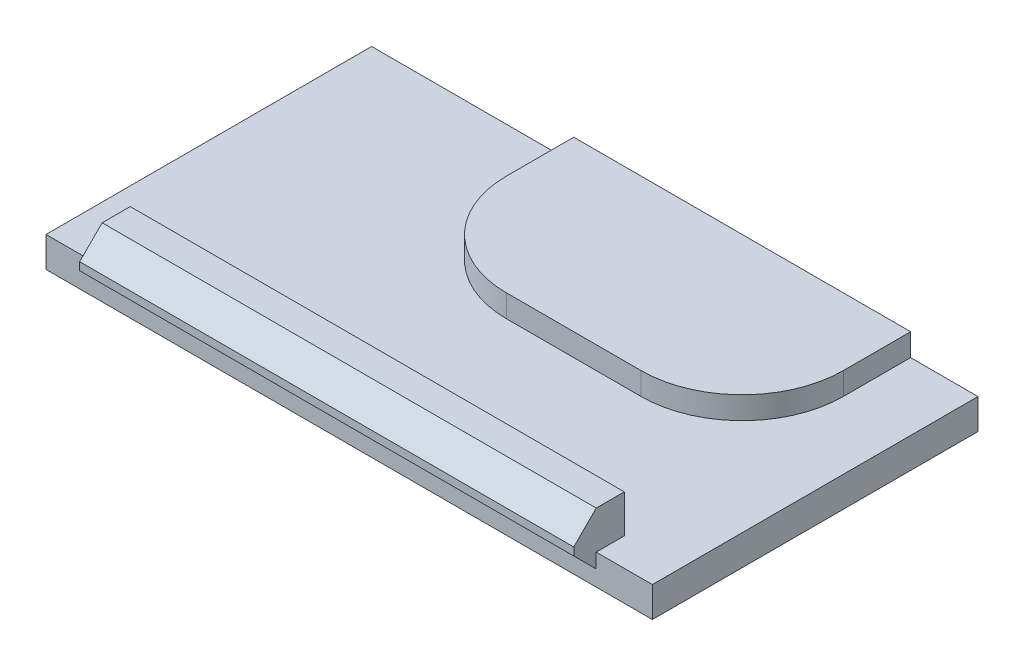
SolidWorks part; units mm, degrees
ref_plane "Front Plane" through (0, 0, 0) normal (0, 0, 1) x (1, 0, 0)
ref_plane "Top Plane" through (0, 0, 0) normal (0, 1, 0) x (1, 0, 0)
ref_plane "Right Plane" through (0, 0, 0) normal (1, 0, 0) x (0, 0, -1)
sketch "Sketch1" plane through (0, 0, 0) normal (0, 1, 0) x (1, 0, 0)
  line L1 (0, 0) -> (68.58, 0)
  line L2 (0, 0) -> (0, 36.83)
  line L3 (0, 36.83) -> (68.58, 36.83)
  line L4 (68.58, 0) -> (68.58, 36.83)
  dimension "D1" = 68.58
  dimension "D2" = 36.83
extrude "Boss-Extrude1" add sketch "Sketch1" along normal blind 3.429
sketch "Sketch3" plane through (0, 0, 0) normal (0, -1, 0) x (1, 0, 0)
  line L0 (34.29, 0) -> (34.29, -21.59) construction
  line L1 (0, 0) -> (68.58, 0) construction
  line L2 (68.58, -36.83) -> (0, -36.83) construction
  line L10 (34.29, -21.59) -> (49.53, -21.59)
  line L11 (57.15, -29.21) -> (57.15, -36.83)
  line L14 (26.67, -29.21) -> (26.67, -36.83)
  line L16 (57.15, -36.83) -> (26.67, -36.83)
  arc A2 (34.29, -21.59) -> (26.67, -29.21) centre (34.29, -29.21) ccw
  arc A3 (57.15, -29.21) -> (49.53, -21.59) centre (49.53, -29.21) ccw
  dimension "D1" = 15.24
  dimension "D3" = 7.62
  dimension "D2" = 15.24
  dimension "D4" = 7.62
  dimension "D5" = 15.24
extrude "Cut-Extrude1" cut sketch "Sketch3" against normal up to surface (3.429 mm away) up to face at (34.29, 3.429, -18.415)
sketch "Sketch5" plane through (0, 0, 0) normal (0, 0, 1) x (1, 0, 0)
  line L0 (0, 3.429) -> (0, 0) construction
  line L1 (6.35, 1.5875) -> (62.23, 1.5875)
  line L2 (6.35, 1.5875) -> (6.35, 7.9375)
  line L3 (6.35, 7.9375) -> (62.23, 7.9375)
  line L4 (62.23, 1.5875) -> (62.23, 7.9375)
  line L5 (68.58, 3.429) -> (68.58, 0) construction
  line L6 (0, 0) -> (68.58, 0) construction
  dimension "D1" = 6.35
  dimension "D2" = 6.35
  dimension "D3" = 1.5875
  dimension "D4" = 6.35
extrude "Boss-Extrude3" add sketch "Sketch5" along normal blind 2.54
chamfer "Chamfer1" distance 2.7305 angle 45 2 edges at (34.29, 1.5875, 2.54) (34.29, 7.9375, 2.54)
sketch "Sketch6" plane through (0, 0, 0) normal (0, 0, -1) x (-1, 0, 0)
  line L5 (-62.23, 7.747) -> (-6.35, 7.747)
  line L6 (-62.23, 7.747) -> (-62.23, 3.429)
  line L7 (-62.23, 3.429) -> (-6.35, 3.429)
  line L8 (-6.35, 7.747) -> (-6.35, 3.429)
extrude "Boss-Extrude4" add sketch "Sketch6" along normal blind 3.175
sketch "Sketch7" plane through (0, 0, 0) normal (0, -1, 0) x (1, 0, 0)
  line L0 (0, -8.255) -> (68.58, -8.255) construction
  line L1 (0, -36.83) -> (0, 0) construction
  line L2 (68.58, 0) -> (68.58, -36.83) construction
  line L4 (49.53, -21.59) -> (34.29, -21.59) construction
  text T0 "<b>BATTERY</b>" font "Arial Rounded MT Bold" height 6.35
  dimension "D1" = 13.335
extrude "Cut-Extrude2" cut sketch "Sketch7" against normal blind 1.016
sketch "Sketch8" plane through (0, 3.429, 0) normal (0, 1, 0) x (1, 0, 0)
  line L0 (60.96, 36.83) -> (60.96, 17.78)
  line L1 (68.58, 36.83) -> (57.15, 36.83) construction
  line L2 (34.29, 17.78) -> (60.96, 17.78)
  line L3 (22.86, 29.21) -> (22.86, 36.83)
  line L4 (26.67, 36.83) -> (0, 36.83) construction
  line L5 (26.67, 29.21) -> (26.67, 36.83) construction
  line L6 (57.15, 36.83) -> (57.15, 29.21) construction
  line L11 (49.53, 21.59) -> (34.29, 21.59) construction
  line L12 (60.96, 36.83) -> (22.86, 36.83)
  arc A0 (22.86, 29.21) -> (34.29, 17.78) centre (34.29, 29.21) ccw
  arc A1 (26.67, 29.21) -> (34.29, 21.59) centre (34.29, 29.21) ccw construction
  arc A2 (49.53, 17.78) -> (60.96, 29.21) centre (49.53, 29.21) ccw
  arc A3 (49.53, 21.59) -> (57.15, 29.21) centre (49.53, 29.21) ccw construction
  line M8 (68.58, 36.83) -> (57.15, 36.83)
  line M9 (57.15, 36.83) -> (57.15, 29.21)
  arc M10 (57.15, 29.21) -> (49.53, 21.59) centre (49.53, 29.21) cw
  line M11 (49.53, 21.59) -> (34.29, 21.59)
  arc M12 (34.29, 21.59) -> (26.67, 29.21) centre (34.29, 29.21) cw
  line M13 (26.67, 29.21) -> (26.67, 36.83)
  line M14 (26.67, 36.83) -> (0, 36.83)
  dimension "D1" = 3.81
  dimension "D2" = 3.81
  dimension "D3" = 3.81
extrude "Boss-Extrude5" add sketch "Sketch8" along normal blind 2.54 contours L2 A2 L0 L3 A0 M8 M9 M10 M11 M12 M13 M14 | L12 M9 M13 M12 M11 M10 region at (60.534, 3.429, -33.02) region at (41.91, 3.429, -29.5455)
sketch "Sketch9" plane through (0, 3.429, 0) normal (0, -1, 0) x (1, 0, 0)
  line L0 (26.67, -36.83) -> (57.15, -36.83)
  line L1 (57.15, -36.83) -> (57.15, -29.21)
  line L2 (49.53, -21.59) -> (34.29, -21.59)
  line L3 (26.67, -36.83) -> (26.67, -29.21)
  arc A0 (26.67, -29.21) -> (34.29, -21.59) centre (34.29, -29.21) cw
  arc A1 (57.15, -29.21) -> (49.53, -21.59) centre (49.53, -29.21) ccw
  arc A2 (34.29, -21.59) -> (26.67, -29.21) centre (34.29, -29.21) ccw construction
  arc A3 (57.15, -29.21) -> (49.53, -21.59) centre (49.53, -29.21) ccw construction
extrude "Cut-Extrude3" cut sketch "Sketch9" against normal blind 0.635
